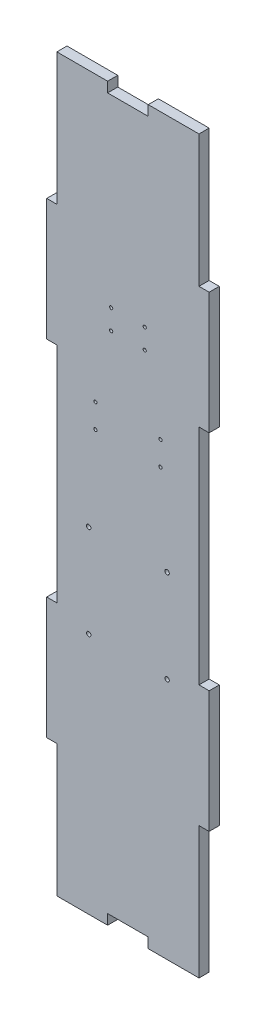
SolidWorks part; units mm, degrees
ref_plane "Front Plane" through (0, 0, 0) normal (0, 0, 1) x (1, 0, 0)
ref_plane "Top Plane" through (0, 0, 0) normal (0, 1, 0) x (1, 0, 0)
ref_plane "Right Plane" through (0, 0, 0) normal (1, 0, 0) x (0, 0, -1)
sketch "Sketch1" plane through (0, 0, 0) normal (0, 0, 1) x (1, 0, 0)
  line L1 (-192.6077, 179.9617) -> (-103.7077, 179.9617)
  line L2 (-192.6077, 179.9617) -> (-192.6077, -277.2383)
  line L3 (-192.6077, -277.2383) -> (-103.7077, -277.2383)
  line L4 (-103.7077, 179.9617) -> (-103.7077, -277.2383)
  dimension "D1" = 457.2
  dimension "D2" = 88.9
extrude "Boss-Extrude1" add sketch "Sketch1" along normal blind 6.35
sketch "Sketch2" plane through (0, 0, 6.35) normal (0, 0, 1) x (1, 0, 0)
  line L0 (-192.6077, 179.9617) -> (-192.6077, -277.2383) construction
  line L1 (-198.9577, 97.4117) -> (-192.6077, 97.4117)
  line L2 (-198.9577, 97.4117) -> (-198.9577, 21.2117)
  line L3 (-198.9577, 21.2117) -> (-192.6077, 21.2117)
  line L4 (-192.6077, 97.4117) -> (-192.6077, 21.2117)
  line L6 (-198.9577, -118.4883) -> (-192.6077, -118.4883)
  line L7 (-198.9577, -118.4883) -> (-198.9577, -194.6883)
  line L8 (-198.9577, -194.6883) -> (-192.6077, -194.6883)
  line L9 (-192.6077, -118.4883) -> (-192.6077, -194.6883)
  line L10 (-148.1577, 179.9617) -> (-148.1577, -277.2383) construction
  line L11 (-103.7077, 179.9617) -> (-192.6077, 179.9617) construction
  line L12 (-192.6077, -277.2383) -> (-103.7077, -277.2383) construction
  line L13 (-97.3577, -194.6883) -> (-103.7077, -194.6883)
  line L14 (-97.3577, -118.4883) -> (-97.3577, -194.6883)
  line L15 (-103.7077, -118.4883) -> (-103.7077, -194.6883)
  line L16 (-97.3577, -118.4883) -> (-103.7077, -118.4883)
  line L17 (-97.3577, 21.2117) -> (-103.7077, 21.2117)
  line L18 (-97.3577, 97.4117) -> (-97.3577, 21.2117)
  line L19 (-103.7077, 97.4117) -> (-103.7077, 21.2117)
  line L20 (-97.3577, 97.4117) -> (-103.7077, 97.4117)
  dimension "D1" = 82.55
  dimension "D4" = 82.55
  dimension "D5" = 6.35
extrude "Boss-Extrude4" add sketch "Sketch2" against normal through all
sketch "Sketch3" plane through (0, 0, 6.35) normal (0, 0, 1) x (1, 0, 0)
  line L0 (-192.6077, -277.2383) -> (-103.7077, -277.2383) construction
  line L1 (-160.8577, -277.2383) -> (-135.4577, -277.2383)
  line L2 (-160.8577, -277.2383) -> (-160.8577, -270.8883)
  line L3 (-160.8577, -270.8883) -> (-135.4577, -270.8883)
  line L4 (-135.4577, -277.2383) -> (-135.4577, -270.8883)
  line L5 (-148.1577, 179.9617) -> (-148.1577, -277.2383) construction
  line L6 (-103.7077, 179.9617) -> (-192.6077, 179.9617) construction
  line L7 (-192.6077, -194.6883) -> (-192.6077, -277.2383) construction
  line L11 (-103.7077, 97.4117) -> (-103.7077, 179.9617) construction
  line L12 (-160.8577, 179.9617) -> (-135.4577, 179.9617)
  line L13 (-160.8577, 179.9617) -> (-160.8577, 173.6117)
  line L14 (-160.8577, 173.6117) -> (-135.4577, 173.6117)
  line L15 (-135.4577, 179.9617) -> (-135.4577, 173.6117)
  dimension "D5" = 6.35
  dimension "D2" = 25.4
  dimension "D3" = 6.35
  dimension "D4" = 25.4
  dimension "D6" = 31.75
  dimension "D1" = 31.75
extrude "Cut-Extrude1" cut sketch "Sketch3" against normal blind 6.35
sketch "Sketch4" plane through (0, 0, 0) normal (0, 0, 1) x (1, 0, 0)
  line L0 (-192.6077, -277.2383) -> (-160.8577, -277.2383) construction
  line L1 (-175.6577, -65.2383) -> (-120.6577, -65.2383) construction
  line L2 (-175.6577, -65.2383) -> (-175.6577, -150.2383) construction
  line L3 (-175.6577, -150.2383) -> (-120.6577, -150.2383) construction
  line L4 (-120.6577, -65.2383) -> (-120.6577, -150.2383) construction
  line L5 (-148.1577, -65.2383) -> (-148.1577, -150.2383) construction
  line L6 (-175.6577, -107.7383) -> (-120.6577, -107.7383) construction
  line L7 (-103.7077, -118.4883) -> (-103.7077, 21.2117) construction
  line L8 (-160.6355, 60.3617) -> (-135.6355, 60.3617) construction
  line L9 (-160.6355, 60.3617) -> (-160.6355, 36.3617) construction
  line L10 (-160.6355, 36.3617) -> (-135.6355, 36.3617) construction
  line L11 (-135.6355, 60.3617) -> (-135.6355, 36.3617) construction
  line L12 (-148.1577, 173.6117) -> (-148.1577, -270.8883) construction
  line L13 (-160.8577, 173.6117) -> (-135.4577, 173.6117) construction
  line L14 (-135.4577, -270.8883) -> (-160.8577, -270.8883) construction
  line L15 (-148.1577, 4.9389) -> (-148.1577, -15.0611) construction
  line L16 (-171.0177, 4.9389) -> (-125.2977, 4.9389) construction
  line L17 (-171.0177, 4.9389) -> (-171.0177, -15.0611) construction
  line L18 (-171.0177, -15.0611) -> (-125.2977, -15.0611) construction
  line L19 (-125.2977, 4.9389) -> (-125.2977, -15.0611) construction
  line L20 (-171.0177, -5.0611) -> (-125.2977, -5.0611) construction
  circle A0 centre (-172.6577, -67.3936) radius 1.375
  circle A1 centre (-123.6577, -67.3936) radius 1.375
  circle A2 centre (-123.6576, -125.3936) radius 1.375
  circle A3 centre (-172.6577, -125.3936) radius 1.375
  circle A4 centre (-158.6355, 58.3617) radius 1
  circle A5 centre (-158.6355, 45.8617) radius 1
  circle A6 centre (-137.6355, 58.3617) radius 1
  circle A7 centre (-137.6355, 45.8617) radius 1
  circle A8 centre (-168.5177, 2.4389) radius 1
  circle A9 centre (-127.7977, 2.4389) radius 1
  circle A10 centre (-127.7977, -12.5611) radius 1
  circle A11 centre (-168.5177, -12.5611) radius 1
  dimension "D5" = 2.75
  dimension "D4" = 2.75
  dimension "D9" = 2
  dimension "D23" = 2
  dimension "D1" = 127
  dimension "D2" = 85
  dimension "D3" = 55
  dimension "D6" = 58
  dimension "D7" = 25
  dimension "D8" = 24
  dimension "D10" = 21
  dimension "D11" = 12.5
  dimension "D12" = 9.5
  dimension "D13" = 2
  dimension "D14" = 2
  dimension "D15" = 2
  dimension "D16" = 31.9278
  dimension "D17" = 101.6
  dimension "D18" = 0
  dimension "D19" = 49
  dimension "D20" = 20
  dimension "D21" = 45.72
  dimension "D22" = 0
  dimension "D24" = 2.5
  dimension "D25" = 2.5
extrude "Cut-Extrude5" cut sketch "Sketch4" against normal through all and the other way through all
equation "\"width\"= 3.5in"
equation "\"Height\"= 18in"
equation "\"thick\"= 0.25"
equation "\"D1@Sketch1\"=\"Height\""
equation "\"D2@Sketch1\"=\"width\""
equation "\"D1@Boss-Extrude1\"=\"thick\""
equation "\"D5@Sketch2\"=\"thick\""
equation "\"D1\"= \"thick\""
equation "\"D3@Sketch3\"=\"thick\""
equation "\"D1@Cut-Extrude1\"=\"thick\""
equation "\"D5@Sketch3\"=\"thick\""
equation "\"D2@Cut-Extrude5\"=\"thick\""
